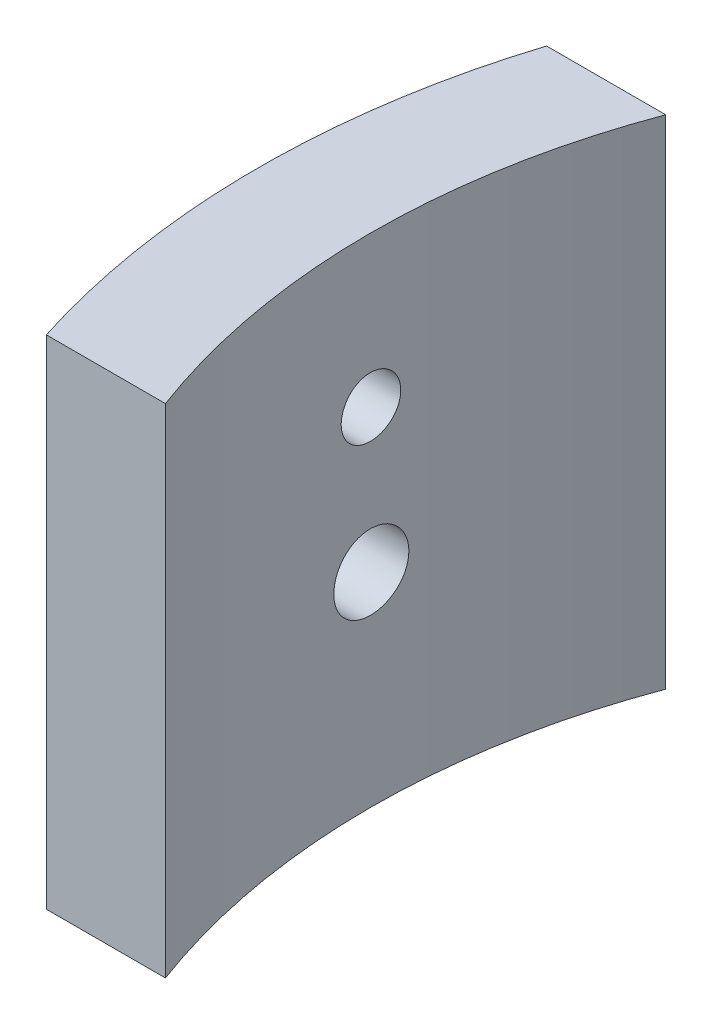
SolidWorks part; units mm, degrees
material "ABS"
ref_plane "Front Plane" through (0, 0, 0) normal (0, 0, 1) x (1, 0, 0)
ref_plane "Top Plane" through (0, 0, 0) normal (0, 1, 0) x (1, 0, 0)
ref_plane "Right Plane" through (0, 0, 0) normal (1, 0, 0) x (0, 0, -1)
sketch "Sketch1" plane through (0, 0, 0) normal (0, 1, 0) x (1, 0, 0)
  line L0 (-42.0402, -13.335) -> (-35.6902, -13.335)
  line L1 (-42.0402, 13.335) -> (-35.6902, 13.335)
  line L2 (-35.6902, 13.335) -> (0, 0) construction
  line L3 (0, 0) -> (-35.6902, -13.335) construction
  line L4 (-88.519, 13.335) -> (-35.6902, 13.335) construction
  arc A0 (-35.6902, 13.335) -> (-35.6902, -13.335) centre (0, 0) ccw
  arc A1 (-42.0402, 13.335) -> (-42.0402, -13.335) centre (0, 0) ccw
  dimension "D1" = 38.1
  dimension "D2" = 6.35
extrude "Boss-Extrude1" add sketch "Sketch1" along normal blind 38.1
ref_plane "Plane1" through (-42.0402, 0, 0) normal (-1, 0, 0) x (0, 0, 1)
sketch "Sketch2" plane through (-42.0402, 0, 0) normal (-1, 0, 0) x (0, 0, 1)
  line L0 (0, 38.1) -> (0, 0) construction
  line L1 (13.335, 38.1) -> (-13.335, 38.1) construction
  circle A0 centre (0, 30.0704) radius 1.5875
  circle A1 centre (0, 30.0704) radius 4.7625
  circle A2 centre (0, 30.0704) radius 1.5875 construction
  dimension "D1" = 3.175
extrude "Boss-Extrude3" add sketch "Sketch2" along normal up to surface (2.4098 mm away)
ref_plane "Plane2" through (-44.1044, 0, 0) normal (-1, 0, 0) x (0, 0, 1)
ref_plane "Plane3" through (-50.4544, 0, 0) normal (-1, 0, 0) x (0, 0, 1)
sketch "Sketch3" plane through (0, 0, 0) normal (0, -1, 0) x (1, 0, 0)
  line L0 (-42.0402, 13.335) -> (-35.6902, 13.335)
  line L1 (-42.0402, -13.335) -> (-35.6902, -13.335)
  arc A0 (-42.0402, 13.335) -> (-42.0402, -13.335) centre (0, 0) ccw
  arc A1 (-35.6902, -13.335) -> (-35.6902, 13.335) centre (0, 0) cw
  arc A2 (-42.0402, 13.335) -> (-42.0402, -13.335) centre (0, 0) ccw construction
  arc A3 (-35.6902, 13.335) -> (-35.6902, -13.335) centre (0, 0) ccw construction
extrude "Cut-Extrude1" cut sketch "Sketch3" against normal up to surface (11.5792 mm away)
sketch "Sketch5" plane through (-44.45, 0, 0) normal (-1, 0, 0) x (0, 0, 1)
  circle A0 centre (0, 30.0704) radius 1.5875
  circle A1 centre (0, 30.0704) radius 1.5875 construction
extrude "Cut-Extrude4" cut sketch "Sketch5" against normal through all
ref_plane "Plane4" through (-35.6902, 0, 0) normal (1, 0, 0) x (0, 0, -1)
sketch "Sketch6" plane through (-35.6902, 0, 0) normal (1, 0, 0) x (0, 0, -1)
  circle A0 centre (0, 22.4504) radius 2
  dimension "D1" = 4
extrude "Cut-Extrude5" cut sketch "Sketch6" against normal up to surface (8.3689 mm away) up to face at (-43.8594, 31.1346, 4.6421)
